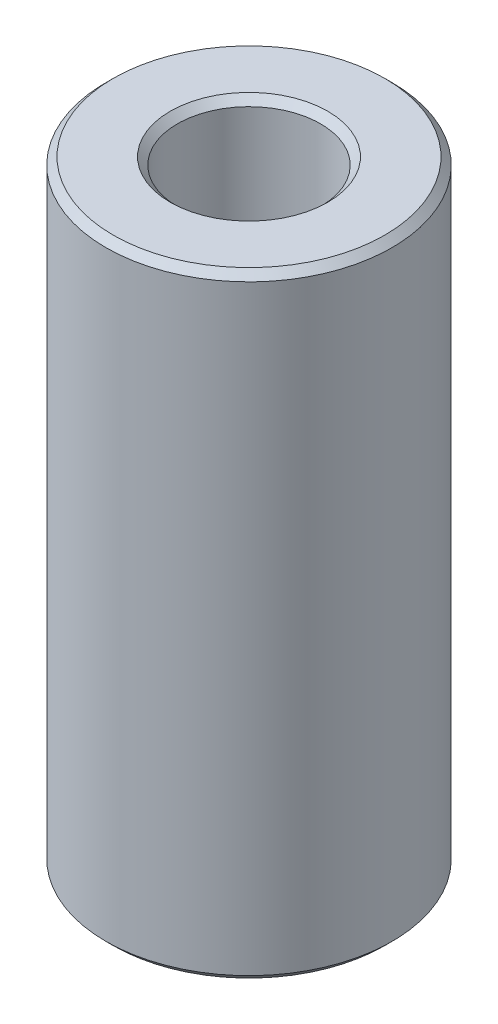
SolidWorks part; units mm, degrees
ref_plane "Front Plane" through (0, 0, 0) normal (0, 0, 1) x (1, 0, 0)
ref_plane "Top Plane" through (0, 0, 0) normal (0, 1, 0) x (1, 0, 0)
ref_plane "Right Plane" through (0, 0, 0) normal (1, 0, 0) x (0, 0, -1)
sketch "Sketch1" plane through (0, 0, 0) normal (0, 1, 0) x (1, 0, 0)
  circle A0 centre (0, 0) radius 12.5
  dimension "SLEEVE_OD" = 25
extrude "Boss-Extrude1" add sketch "Sketch1" along normal blind 53.7752
sketch "Sketch2" plane through (0, 0, 0) normal (0, 1, 0) x (1, 0, 0)
  circle A0 centre (0, 0) radius 6.2573
  dimension "BORE_D" = 12.5146
extrude "Cut-Extrude1" cut sketch "Sketch2" along normal through all
chamfer "Chamfer1" distance 0.6324 angle 45 4 edges at (0, 53.7752, 6.2573) (0, 0, 6.2573) (0, 0, 12.5) (0, 53.7752, 12.5)
